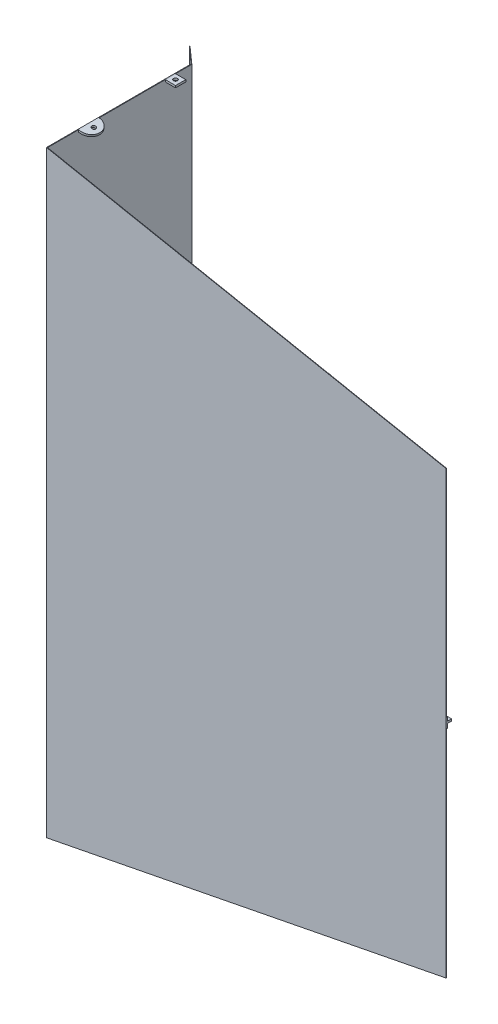
SolidWorks part; units mm, degrees
note: The reader was unsure of these and kept them because the rebuilt part matched: shared geometry of "Szkic6<2>".
material "Stop 6061"
ref_plane "Płaszczyzna XY" through (0, 0, 0) normal (0, 0, 1) x (1, 0, 0)
ref_plane "Płaszczyzna XZ" through (0, 0, 0) normal (0, 1, 0) x (1, 0, 0)
ref_plane "Płaszczyzna YZ" through (0, 0, 0) normal (1, 0, 0) x (0, 0, -1)
ref_plane "Płaszczyzna2" through (260.8517, 0, -234.8719) normal (-0.7431, 0, 0.6691) x (0.6691, 0, 0.7431)
sketch "Szkic1" plane through (0, 0, 0) normal (0, 1, 0) x (1, 0, 0)
  line L0 (956.9507, -465.2284) -> (970.5827, -477.0593)
  line L1 (970.5827, -477.0593) -> (970.5827, -617.9993)
  line L2 (970.5827, -617.9993) -> (1360.0727, -617.9993)
  dimension "D1" = 617.9993
  dimension "D2" = 18.05
  dimension "D3" = 140.94
  dimension "D4" = 389.49
  dimension "D5" = 1360.0727
  dimension "D6" = 130.954
ref_plane "Płaszczyzna1" through (0, 0, 614.2832) normal (0, 0, 1) x (1, 0, 0)
sketch "Szkic2" plane through (0, 0, 614.2832) normal (0, 0, 1) x (1, 0, 0)
  line L0 (1356.4214, 217.4086) -> (1036.2864, 217.4086) construction
  line L1 (84.299, 0) -> (-84.299, 0) construction
  line L2 (1356.4214, -217.4086) -> (1036.2864, -217.4086) construction
  dimension "D1" = 1036.2864
  dimension "D2" = 320.135
  dimension "D3" = 217.4086
extrude "Wyciągnięcie-cienka ścianka1" add sketch "Szkic1" along normal blind 400 and the other way blind 400 thin thin type one direction wall 0.5
ref_plane "Płaszczyzna3" through (0, 217.4086, 0) normal (0, 1, 0) x (-1, 0, 0)
ref_plane "Płaszczyzna4" through (0, -217.4086, 0) normal (0, 1, 0) x (-1, 0, 0)
ref_plane "Płaszczyzna5" through (90.906, -464.0758, 0) normal (-0.1922, 0.9813, 0) x (-0.9813, -0.1922, 0)
ref_plane "Płaszczyzna6" through (90.906, 464.0758, 0) normal (0.1922, 0.9813, 0) x (-0.9813, 0.1922, 0)
other "Cięcie powierzchnią1" flip cut yes
other "Cięcie powierzchnią2"
ref_plane "Płaszczyzna7" through (0, 0, 617.9993) normal (0, 0, -1) x (-1, 0, 0)
ref_plane "Płaszczyzna8" through (90.906, -464.0758, 0) normal (0.1922, -0.9813, 0) x (-0.9813, -0.1922, 0)
ref_plane "Płaszczyzna9" through (90.906, -464.0758, 0) normal (0.1922, -0.9813, 0) x (-0.9813, -0.1922, 0)
sketch "Szkic4" plane through (90.906, -464.0758, 0) normal (0.1922, -0.9813, 0) x (-0.9813, -0.1922, 0)
  line L1 (-896.395, -617.9993) -> (-896.395, -477.0593) construction
  line L4 (-896.395, -587.6699) -> (-896.395, -567.6463)
  arc A0 (-896.395, -587.6699) -> (-896.395, -567.6463) centre (-897.3784, -577.6581) cw
  dimension "D2" = 20.0236
  dimension "D3" = 587.6699
  dimension "D1" = 10.06
extrude "Dodanie-wyciągnięcie2" add sketch "Szkic4" against normal blind 2
sketch "Szkic6" plane through (0, 0, 0) normal (0, 1, 0) x (1, 0, 0)
  line L0 (970.5827, -617.9993) -> (1360.0727, -617.9993)
extrude "Wyciągnięcie-cienka ścianka2" add sketch "Szkic6" along normal blind 1 and the other way blind 1 thin thin type one direction reverse wall 5
extrude "Wyciągnięcie-cienka ścianka3" add sketch "Szkic6<2>" along normal blind 5 and the other way blind 5 thin thin type one direction reverse wall 1
sketch "Szkic6<2>" plane through (0, 0, 0) normal (0, 1, 0) x (1, 0, 0) same geometry as "Szkic6"
ref_plane "Płaszczyzna10" through (90.5216, -462.1131, 0) normal (-0.1922, 0.9813, 0) x (0.9813, 0.1922, 0)
sketch "Szkic7" plane through (90.5216, -462.1131, 0) normal (-0.1922, 0.9813, 0) x (0.9813, 0.1922, 0)
  line L0 (896.395, -617.9993) -> (896.395, -587.6699) construction
  circle A0 centre (901.1177, -577.4282) radius 2
  dimension "D1" = 4
  dimension "D2" = 4.7227
  dimension "D3" = 10.2417
extrude "Wytnij-wyciągnięcie1" cut sketch "Szkic7" against normal blind 10
mirror "Lustro1" about plane through (0, 0, 0) normal (0, 1, 0) of "Dodanie-wyciągnięcie2", "Wytnij-wyciągnięcie1"
ref_plane "Płaszczyzna12" through (970.5827, 0, 0) normal (1, 0, 0) x (0, 0, -1)
sketch "Szkic9" plane through (970.5827, 0, 0) normal (1, 0, 0) x (0, 0, -1)
  line L0 (-502.9993, -291.7593) -> (-492.9993, -291.7593)
  line L1 (-567.6463, -291.7593) -> (-477.0593, -291.7593) construction
extrude "Wyciągnięcie-cienka ścianka4" add sketch "Szkic9" along normal blind 10 thin thin type one direction reverse wall 2
ref_plane "Płaszczyzna13" through (0, -289.7593, 0) normal (0, 1, 0) x (1, 0, 0)
sketch "Szkic10" plane through (0, -289.7593, 0) normal (0, 1, 0) x (1, 0, 0)
  line L0 (980.5827, -492.9993) -> (970.5827, -492.9993) construction
  line L1 (980.5827, -502.9993) -> (980.5827, -492.9993) construction
  circle A0 centre (975.5827, -497.9993) radius 2
  dimension "D1" = 4
  dimension "D2" = 5
  dimension "D3" = 5
extrude "Wytnij-wyciągnięcie2" cut sketch "Szkic10" against normal blind 10
ref_plane "Plane1" through (0, 0, 617.9993) normal (0, 0, -1) x (-1, 0, 0)
sketch "Sketch1" plane through (0, 0, 617.9993) normal (0, 0, -1) x (-1, 0, 0)
  line L0 (-1360.0727, -215.4636) -> (-970.5827, -291.7593) construction
  line L1 (-1360.0727, -215.4636) -> (-1360.0727, -5) construction
  circle A0 centre (-1233.5042, -222.0341) radius 4
  dimension "D1" = 8
  dimension "D2" = 17.8827
  dimension "D3" = 126.5685
extrude "Boss-Extrude1" add sketch "Sketch1" along normal blind 12
mirror "Lustro2" about plane through (0, 0, 0) normal (0, 1, 0) of "Boss-Extrude1", "Wyciągnięcie-cienka ścianka4", "Wytnij-wyciągnięcie2"
